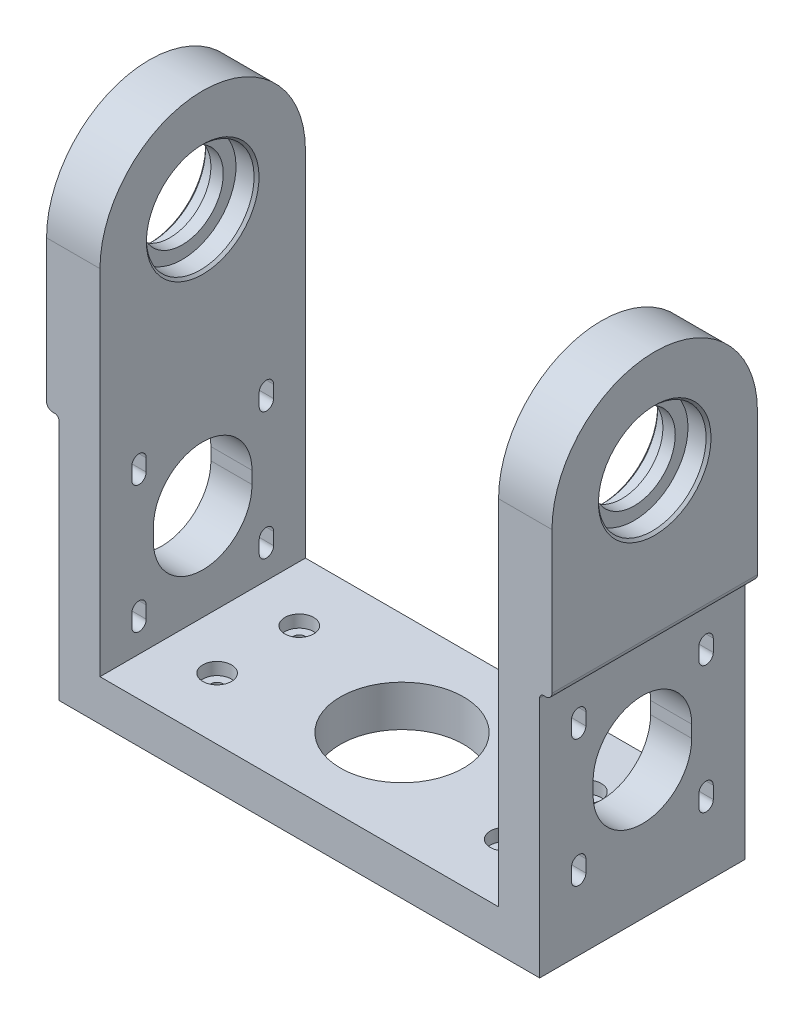
SolidWorks part; units mm, degrees
ref_plane "Front Plane" through (0, 0, 0) normal (0, 0, 1) x (1, 0, 0)
ref_plane "Top Plane" through (0, 0, 0) normal (0, 1, 0) x (1, 0, 0)
ref_plane "Right Plane" through (0, 0, 0) normal (1, 0, 0) x (0, 0, -1)
sketch "Sketch1" plane through (0, 0, 0) normal (0, 0, 1) x (1, 0, 0)
  line L0 (10, 128) -> (-3, 128)
  line L1 (0, 0) -> (117, 0)
  line L3 (10, 10) -> (107, 10)
  line L6 (0, 0) -> (0, 59)
  line L8 (10, 10) -> (10, 128)
  line L10 (117, 0) -> (117, 59)
  line L12 (107, 10) -> (107, 128)
  line L13 (-3, 128) -> (-3, 61.5)
  line L14 (-1.5, 60) -> (-1, 60)
  line L15 (107, 128) -> (120, 128)
  line L16 (120, 128) -> (120, 61.5)
  line L17 (118.5, 60) -> (118, 60)
  arc A0 (120, 61.5) -> (118.5, 60) centre (118.5, 61.5) cw
  arc A1 (-3, 61.5) -> (-1.5, 60) centre (-1.5, 61.5) ccw
  arc A2 (117, 59) -> (118, 60) centre (118, 59) cw
  arc A3 (0, 59) -> (-1, 60) centre (-1, 59) ccw
  point P15 (120, 60)
  point P18 (-3, 60)
  point P22 (117, 60)
  point P25 (0, 60)
  dimension "D8" = 1.5
  dimension "D9" = 1
  dimension "D1" = 97
  dimension "D2" = 10
  dimension "D3" = 10
  dimension "D4" = 118
  dimension "D5" = 3
  dimension "D6" = 3
  dimension "D7" = 60
extrude "Boss-Extrude1" add sketch "Sketch1" along normal blind 50
sketch "Sketch2" plane through (117, 0, 0) normal (1, 0, 0) x (0, 0, -1)
  line L0 (-42.25, 47.5) -> (-42.25, 50.5)
  line L1 (-50, 0) -> (0, 0) construction
  line L2 (-38.75, 50.5) -> (-38.75, 47.5)
  line L3 (-37, 35) -> (-37, 32)
  line L4 (-13, 35) -> (-13, 32)
  line L5 (-11.25, 50.5) -> (-11.25, 47.5)
  line L6 (-7.75, 50.5) -> (-7.75, 47.5)
  line L7 (-11.25, 19.5) -> (-11.25, 16.5)
  line L8 (-7.75, 19.5) -> (-7.75, 16.5)
  line L9 (-38.75, 19.5) -> (-38.75, 16.5)
  line L10 (-42.25, 19.5) -> (-42.25, 16.5)
  arc A0 (-13, 35) -> (-37, 35) centre (-25, 35) ccw
  arc A1 (-38.75, 50.5) -> (-42.25, 50.5) centre (-40.5, 50.5) ccw
  arc A2 (-7.75, 50.5) -> (-11.25, 50.5) centre (-9.5, 50.5) ccw
  arc A3 (-7.75, 19.5) -> (-11.25, 19.5) centre (-9.5, 19.5) ccw
  arc A4 (-38.75, 19.5) -> (-42.25, 19.5) centre (-40.5, 19.5) ccw
  arc A5 (-37, 32) -> (-13, 32) centre (-25, 32) ccw
  arc A6 (-42.25, 47.5) -> (-38.75, 47.5) centre (-40.5, 47.5) ccw
  arc A7 (-11.25, 47.5) -> (-7.75, 47.5) centre (-9.5, 47.5) ccw
  arc A8 (-11.25, 16.5) -> (-7.75, 16.5) centre (-9.5, 16.5) ccw
  arc A9 (-42.25, 16.5) -> (-38.75, 16.5) centre (-40.5, 16.5) ccw
  point P12 (-25, 0)
  dimension "D1" = 3.5
  dimension "D4" = 24
  dimension "D8" = 3.5
  dimension "D11" = 24
  dimension "D2" = 31
  dimension "D3" = 31
  dimension "D5" = 15.5
  dimension "D6" = 15.5
  dimension "D7" = 35
  dimension "D9" = 31
  dimension "D10" = 31
  dimension "D12" = 15.5
  dimension "D13" = 15.5
  dimension "D14" = 3
extrude "Cut-Extrude1" cut sketch "Sketch2" against normal through all
sketch "Sketch3" plane through (120, 0, 0) normal (1, 0, 0) x (0, 0, -1)
  line L0 (-50, 128) -> (0, 128) construction
  circle A0 centre (-25, 96) radius 13.1
  point P4 (-25, 128)
  dimension "D1" = 26.2
  dimension "D2" = 32
extrude "Cut-Extrude2" cut sketch "Sketch3" against normal blind 5
extrude "Cut-Extrude3" cut sketch "Sketch3<3>" along normal blind 5 from surface starting at face at (-3, 94.75, 25)
sketch "Sketch3<3>" plane through (120, 0, 0) normal (1, 0, 0) x (0, 0, -1) same geometry as "Sketch3"
extrude "Cut-Extrude4" cut sketch "Sketch3<4>" along normal blind 5 from surface starting at face at (107, 33.5, 25)
sketch "Sketch3<4>" plane through (120, 0, 0) normal (1, 0, 0) x (0, 0, -1) same geometry as "Sketch3"
extrude "Cut-Extrude5" cut sketch "Sketch3<5>" against normal blind 5 from surface starting at face at (10, 33.5, 25)
sketch "Sketch3<5>" plane through (120, 0, 0) normal (1, 0, 0) x (0, 0, -1) same geometry as "Sketch3"
sketch "Sketch4" plane through (115, 0, 0) normal (1, 0, 0) x (0, 0, -1)
  circle A0 centre (-25, 96) radius 10
extrude "Cut-Extrude6" cut sketch "Sketch4" against normal through all
chamfer "Chamfer1" distance 0.6 angle 45 4 edges at (-3, 109.1, 25) (107, 96, 11.9) (120, 96, 11.9) (10, 82.9, 25)
sketch "Sketch5" plane through (-3, 0, 0) normal (-1, 0, 0) x (0, 0, 1)
  line L0 (0, 96) -> (0, 151.7108)
  line L1 (0, 151.7108) -> (50, 151.7108)
  line L2 (50, 151.7108) -> (50, 96)
  arc A0 (50, 96) -> (0, 96) centre (25, 96) ccw
  dimension "D1" = 50
extrude "Cut-Extrude7" cut sketch "Sketch5" against normal through all
sketch "Sketch6" plane through (0, 0, 0) normal (0, -1, 0) x (-1, 0, 0)
  line L0 (0, -50) -> (-117, -50) construction
  line L1 (0, -50) -> (0, 0) construction
  circle A0 centre (-58.5, -25) radius 50
  circle A1 centre (-68.5, 10) radius 1.5
  circle A2 centre (-48.5, 10) radius 1.5
  circle A3 centre (-68.5, -60) radius 1.5
  circle A4 centre (-48.5, -60) radius 1.5
  circle A7 centre (-23.5, -15) radius 1.5
  circle A8 centre (-23.5, -35) radius 1.5
  circle A9 centre (-93.5, -35) radius 1.5
  circle A10 centre (-93.5, -15) radius 1.5
  circle A11 centre (-48.5, -60) radius 1.5
  circle A12 centre (-68.5, -60) radius 1.5
  circle A13 centre (-68.5, 10) radius 1.5
  circle A14 centre (-48.5, 10) radius 1.5
  circle A15 centre (-93.5, -35) radius 1.5
  circle A16 centre (-93.5, -15) radius 1.5
  circle A17 centre (-23.5, -15) radius 1.5
  circle A18 centre (-23.5, -35) radius 1.5
  point P4 (-58.5, -50)
  point P7 (0, -25)
  point P42 (-58.5, -25)
  dimension "D1" = 100
  dimension "D6" = 3
  dimension "D2" = 20
  dimension "D3" = 35
  dimension "D4" = 10
  dimension "D5" = 35
  dimension "D7" = 4
sketch "Sketch7" plane through (0, 10, 0) normal (0, 1, 0) x (1, 0, 0)
  circle A0 centre (58.5, -25) radius 15
  dimension "D1" = 30
extrude "Cut-Extrude8" cut sketch "Sketch7" against normal blind 10
extrude "Cut-Extrude9" cut sketch "Sketch6" against normal blind 10 contours A10 | A9 | A8 | A7 region at (23.5, 0, 15) region at (23.5, 0, 35) region at (93.5, 0, 35) region at (93.5, 0, 15)
sketch "Sketch8" plane through (0, 10, 0) normal (0, 1, 0) x (1, 0, 0)
  circle A0 centre (23.5, -15) radius 3.5
  circle A1 centre (23.5, -35) radius 3.5
  circle A2 centre (93.5, -35) radius 3.5
  circle A3 centre (93.5, -15) radius 3.5
  dimension "D1" = 7
extrude "Cut-Extrude10" cut sketch "Sketch8" against normal blind 3
